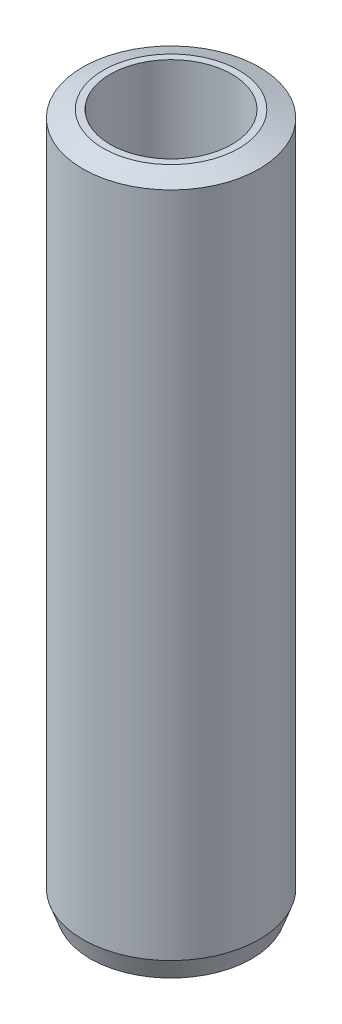
SolidWorks part; units mm, degrees
ref_plane "Front Plane" through (0, 0, 0) normal (0, 0, 1) x (1, 0, 0)
ref_plane "Top Plane" through (0, 0, 0) normal (0, 1, 0) x (1, 0, 0)
ref_plane "Right Plane" through (0, 0, 0) normal (1, 0, 0) x (0, 0, -1)
sketch "Sketch1" plane through (0, 0, 0) normal (0, 1, 0) x (1, 0, 0)
  circle A0 centre (0, 0) radius 27.5
  dimension "SHAFT_OD" = 55
extrude "Boss-Extrude1" add sketch "Sketch1" along normal blind 216.737
sketch "Sketch2" plane through (0, 0, 0) normal (0, 1, 0) x (1, 0, 0)
  circle A0 centre (0, 0) radius 18.9655
  dimension "BORE_D" = 37.931
extrude "Cut-Extrude1" cut sketch "Sketch2" along normal through all
chamfer "Chamfer1" distance 2.336 angle 69.889 2 edges at (0, 216.737, 27.5) (0, 0, 27.5) first distance on face at (0, 216.737, 27.5) first distance on face at (0, 0, 18.9655)
